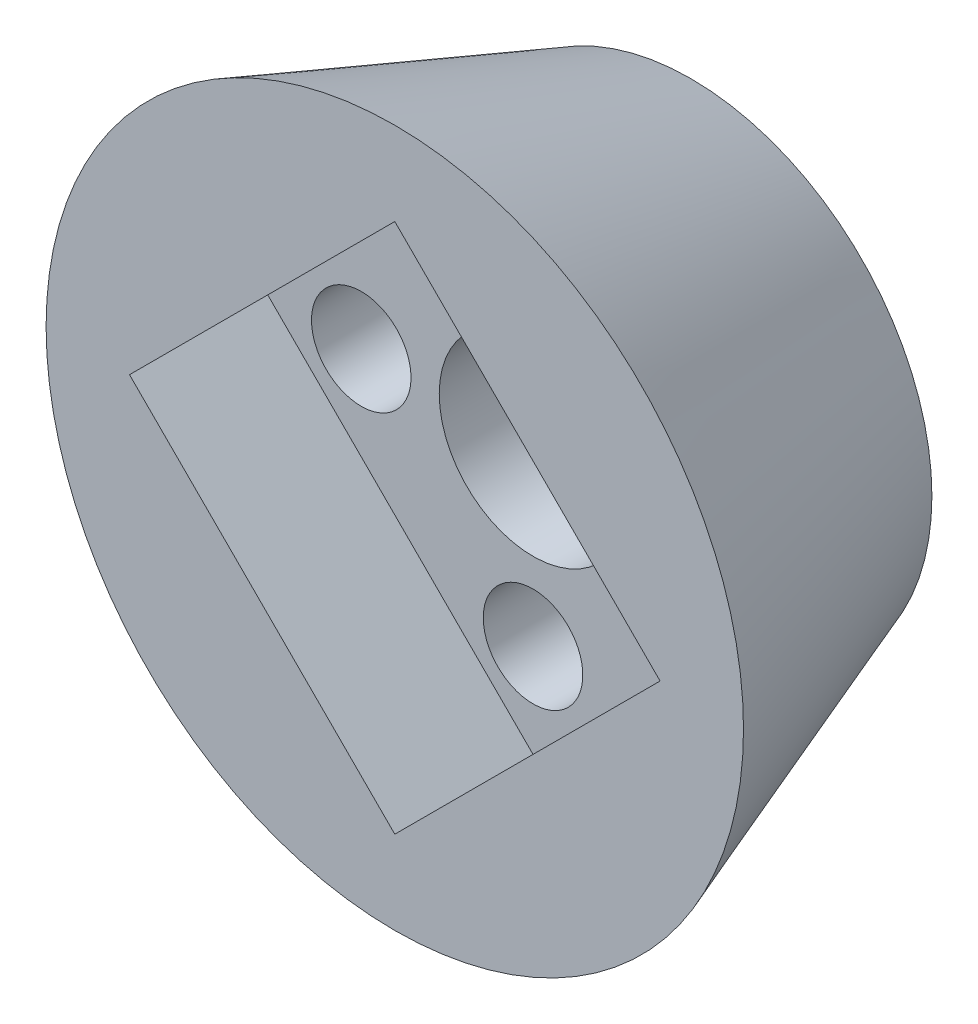
SolidWorks part; units mm, degrees
ref_plane "Front" through (0, 0, 0) normal (0, 0, 1) x (1, 0, 0)
ref_plane "Top" through (0, 0, 0) normal (0, 1, 0) x (1, 0, 0)
ref_plane "Right" through (0, 0, 0) normal (1, 0, 0) x (0, 0, -1)
sketch "GearFaceProfile" plane through (0, 0, 0) normal (0, 0, 1) x (1, 0, 0)
  circle A0 centre (0, 0) radius 12.2
  dimension "D1" = 24.4
extrude "GearFaceExtrude" add sketch "GearFaceProfile" along normal blind 15 draft 20 draft outward yes
sketch "CenterHoleProfile" plane through (0, 0, 0) normal (0, 0, -1) x (-1, 0, 0)
  circle A0 centre (0, 0) radius 4.75
  dimension "D1" = 9.5
extrude "CenterHoleCut" cut sketch "CenterHoleProfile" against normal through all
sketch "ScrewHoleProfile" plane through (0, 0, 0) normal (0, 0, -1) x (-1, 0, 0)
  line L0 (0, 0) -> (0, 8.7) construction
  line L1 (0, 0) -> (8.7, 0) construction
  line L2 (0, 0) -> (0, -8.7) construction
  line L3 (0, 0) -> (-8.7, 0) construction
  circle A2 centre (0, 8.7) radius 2.52
  circle A3 centre (8.7, 0) radius 2.52
  circle A4 centre (0, -8.7) radius 2.52
  circle A5 centre (-8.7, 0) radius 2.52
  dimension "D5" = 5.04
  dimension "D6" = 5.04
  dimension "D7" = 5.04
  dimension "D8" = 5.04
  dimension "D1" = 8.7
  dimension "D2" = 8.7
  dimension "D3" = 8.7
  dimension "D4" = 8.7
extrude "ScrewHoleCut" cut sketch "ScrewHoleProfile" against normal through all
sketch "ShaftCollarAttachmentProfile" plane through (0, 0, 15) normal (0, 0, 1) x (1, 0, 0)
  line L0 (0, 0) -> (0, 13.435) construction
  line L1 (0, 0) -> (13.435, 0) construction
  line L2 (0, 13.435) -> (13.435, 0)
  line L3 (13.435, 0) -> (0, -13.435)
  line L4 (0, -13.435) -> (-13.435, 0)
  line L5 (-13.435, 0) -> (0, 13.435)
  dimension "D1" = 19
  dimension "D2" = 19
extrude "ShaftCollarDockingCut" cut sketch "ShaftCollarAttachmentProfile" against normal blind 7
equation "\"TGMScrewHole-Center\"=8.70mm"
equation "\"TGMScrewHoleDiameter\"=5.04mm"
equation "\"TGMCenterHoleDiameter\"=9.50mm"
equation "\"TGMGearFaceDiameter\"=24.40mm"
equation "\"D1@GearFaceProfile\" = \"TGMGearFaceDiameter\""
equation "\"D1@CenterHoleProfile\" = \"TGMCenterHoleDiameter\""
equation "\"D4@ScrewHoleProfile\" = \"TGMScrewHole-Center\""
equation "\"D1@ScrewHoleProfile\" = \"TGMScrewHole-Center\""
equation "\"D2@ScrewHoleProfile\" = \"TGMScrewHole-Center\""
equation "\"D3@ScrewHoleProfile\" = \"TGMScrewHole-Center\""
equation "\"D5@ScrewHoleProfile\" = \"TGMScrewHoleDiameter\""
equation "\"D6@ScrewHoleProfile\" = \"TGMScrewHoleDiameter\""
equation "\"D8@ScrewHoleProfile\" = \"TGMScrewHoleDiameter\""
equation "\"D7@ScrewHoleProfile\" = \"TGMScrewHoleDiameter\""
equation "\"TGMCylinderLength\"=15.00mm"
equation "\"TGMShaftCollarSideLength\"=19.00mm"
equation "\"D1@ShaftCollarAttachmentProfile\" = \"TGMShaftCollarSideLength\""
equation "\"D2@ShaftCollarAttachmentProfile\" = \"TGMShaftCollarSideLength\""
equation "\"TGMShaftCollarDockingDepth\"=7.00mm"
equation "\"CageLeftBottomEdge\"=21.15mm"
equation "\"CageLeftTopEdge\"=22.11mm"
equation "\"CageRightBottomEdge\"=21.20mm"
equation "\"CageRightTopEdge\"=21.63mm"
equation "\"CageHeight\"=86.04mm"
equation "\"CageLength\"=73.76mm"
equation "\"CageTopScrewClearance\"=10mm"
equation "\"CageBottomScrewClearance\"=25mm"
equation "\"CageLeftTopDepth\"= 11.65mm"
equation "\"CageLeftBottomDepth\"=10.15mm"
equation "\"CageLeftTopHeight\"=10.56175mm"
equation "\"CageLeftBottomHeight\"=16mm"
equation "\"CageRightTopDepth\"= 11.15mm"
equation "\"CageRightBottomDepth\"=10.15mm"
equation "\"CageRightTopHeight\"=9.775mm"
equation "\"CageRightBottomHeight\"=15.49mm"
equation "\"CageLeftTopChannelDepth\"=2.41908mm"
equation "\"CageLeftBottomChannelDepth\"=2.588mm"
equation "\"CageLeftChannelHeight\"=11.7mm"
equation "\"CageRightTopChannelDepth\"=2.59mm"
equation "\"CageRightBottomChannelDepth\"=2.318mm"
equation "\"CageRightChannelHeight\"=10mm"
equation "\"CageChanRelHeight\"=23.99mm"
equation "\"CageChanRelDepth\"=5.492mm"
equation "\"CageChamberRadius\"=16.261mm"
equation "\"CageScrewDiameter\"=4.8mm"
equation "\"CageSetScrewDiameter\"=3.5mm"
equation "\"CageAxleRadius\"=6.639mm"
equation "\"CageAxleKeyHeight\"=1.619mm"
equation "\"CageAxleKeyWidth\"=2.662mm"
equation "\"CageHoseWindowWidth\"=16.29mm"
equation "\"CageHoseWindowHeight\"=26.5mm"
equation "\"CageHoseWindow-Edge\"=8.89mm"
equation "\"CageScrew-VerticalEdge\"=5.0mm"
equation "\"CageScrew-HorizontalEdge\"=7.5mm"
equation "\"CageScrew-HoseCornerScrewEdge\"=4.45mm"
equation "\"CageAxle-BottomEdge\"=56.05mm"
equation "\"CageAxle-FrontEdge\"=46.03mm"
equation "\"CageBackSetScrew-Axle\"=40mm"
equation "\"CageFrontSetScrew-Axle\"=22mm"
equation "\"CageVelocityWindow-BackEdge\"=34.8mm"
equation "\"CageVelocityWindow-BottomEdge\"=27.55mm"
equation "\"CageVelocityWindowHeight\"=22.29mm"
equation "\"CageVelocityWindowWidth\"=12.61mm"
equation "\"TriggerSlot-BottomEdge\"=6.35mm"
equation "\"TriggerSlot-FrontEdge\"=15mm"
equation "\"TriggerSlotSize\"=6.7mm"
equation "\"vigorwidth\"= 0.472441in"
equation "\"vigorflangewidth\"= 0.731102in"
equation "\"vigorflangelength\"= 0.131102in"
equation "\"vigorscrewsize\"= 0.066535in"
equation "\"vigorholeoffsetwid\"= 0.0646653in"
equation "\"vigorholeoffsetlen\"= 0.065551in"
equation "\"vigorflangedepth\"= 0.0901575in"
equation "\"vigordiscdepth\"= 0.0492126in"
equation "\"vigormotordepth\"= 1.12362in"
equation "\"vigortipdepth\"= 0.259055in"
equation "\"vigoraxlewidth\"= 0.173622in"
equation "\"vigorcutlen\"= 0.0480315in"
equation "\"vigoraxledepth\"= 0.159055in"
equation "\"TriggerRackOffset\"=.236224in"
equation "\"TriggerSlotSizeInt\"=.25in"
equation "\"MotorMountLegLength\"=.25in"
equation "\"GearOffset\"=.264907in"
equation "\"TriggerSlotSpacing\"=.25in"
